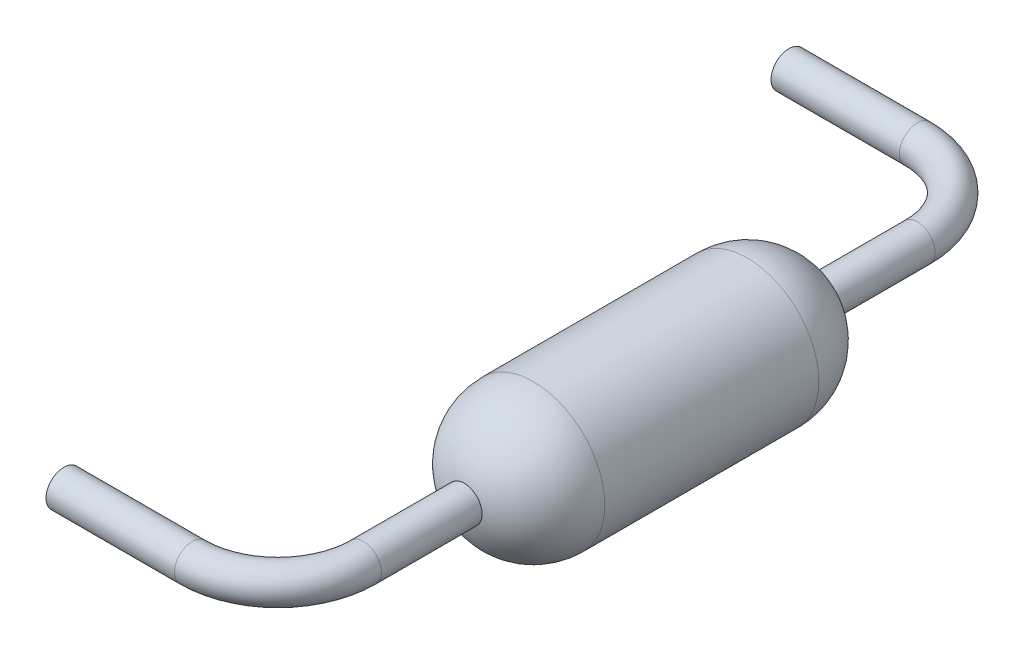
SolidWorks part; units mm, degrees
ref_plane "Front Plane" through (0, 0, 0) normal (0, 0, 1) x (1, 0, 0)
ref_plane "Top Plane" through (0, 0, 0) normal (0, 1, 0) x (1, 0, 0)
ref_plane "Right Plane" through (0, 0, 0) normal (1, 0, 0) x (0, 0, -1)
sketch "Sketch1" plane through (0, 0, 0) normal (0, 0, 1) x (1, 0, 0)
  circle A0 centre (0, 0) radius 1
  dimension "D1" = 2
extrude "Boss-Extrude1" add sketch "Sketch1" along normal mid plane 3
dome "Dome1" faces to dome 1 distance 1 reverse direction no elliptical dome no face at (1, 0, 1.5) parameters "D1"=1
dome "Dome2" faces to dome 1 distance 1 reverse direction no elliptical dome no face at (1, 0, -1.5) parameters "D1"=1
sketch "Sketch3" plane through (0, 0, 0) normal (0, 1, 0) x (1, 0, 0)
  line L0 (0, -3.88) -> (0, 3.88)
  line L1 (-1.2, -5.08) -> (-3, -5.08)
  line L2 (-1.2, 5.08) -> (-3, 5.08)
  arc A0 (0, 3.88) -> (-1.2, 5.08) centre (-1.2, 3.88) ccw
  arc A1 (0, -3.88) -> (-1.2, -5.08) centre (-1.2, -3.88) cw
  point P4 (0, 0)
  point P9 (0, 5.08)
  point P12 (0, -5.08)
  dimension "D3" = 1.2
  dimension "D1" = 10.16
  dimension "D2" = 3
sketch "Sketch4" plane through (0, 0, 0) normal (0, 0, 1) x (1, 0, 0)
  circle A0 centre (0, 0) radius 0.25
  dimension "D1" = 0.5
sweep "Sweep1" add profiles "Sketch4" path "Sketch3"
